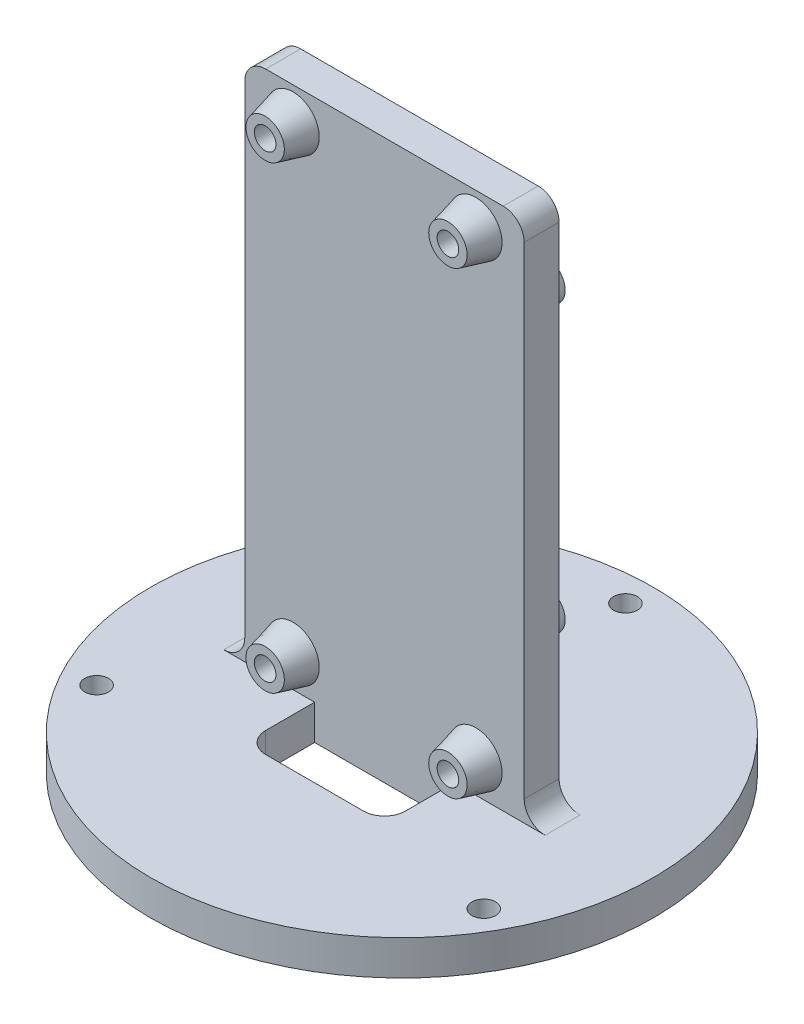
SolidWorks part; units mm, degrees
ref_plane "Front Plane" through (0, 0, 0) normal (0, 0, 1) x (1, 0, 0)
ref_plane "Top Plane" through (0, 0, 0) normal (0, 1, 0) x (1, 0, 0)
ref_plane "Right Plane" through (0, 0, 0) normal (1, 0, 0) x (0, 0, -1)
sketch "Sketch1" plane through (0, 0, 0) normal (0, 1, 0) x (1, 0, 0)
  circle A0 centre (0, 0) radius 36
  circle A1 centre (0, 32) radius 1.7
  circle A2 centre (0, 0) radius 32 construction
  circle A3 centre (27.7128, -16) radius 1.7
  circle A4 centre (-27.7128, -16) radius 1.7
  point P13 (0, 0)
  dimension "D1" = 64
  dimension "D2" = 72
  dimension "D3" = 3.4
  dimension "D4" = 3
extrude "Boss-Extrude1" add sketch "Sketch1" along normal blind 5
sketch "Sketch2" plane through (0, 0, 0) normal (0, 0, 1) x (1, 0, 0)
  line L0 (36, 5) -> (-36, 5) construction
  line L1 (-20, 5) -> (20, 5)
  line L2 (-20, 5) -> (-20, 80)
  line L3 (-20, 80) -> (20, 80)
  line L4 (20, 5) -> (20, 80)
  line L5 (0, 0) -> (0, 80) construction
  dimension "D1" = 40
  dimension "D2" = 75
extrude "Boss-Extrude2" add sketch "Sketch2" along normal mid plane 5
sketch "Sketch3" plane through (0, 0, 2.5) normal (0, 0, 1) x (1, 0, 0)
  line L0 (0, 80) -> (0, 0) construction
  line L1 (20, 80) -> (-20, 80) construction
  line L2 (-20, 42.5) -> (20, 42.5) construction
  line L3 (-13.085, 9.625) -> (13.085, 9.625) construction
  line L4 (-13.085, 9.625) -> (-13.085, 75.375) construction
  line L5 (-13.085, 75.375) -> (13.085, 75.375) construction
  line L6 (13.085, 9.625) -> (13.085, 75.375) construction
  line L7 (-13.085, 9.625) -> (13.085, 75.375) construction
  line L8 (-13.085, 75.375) -> (13.085, 9.625) construction
  line L9 (-20, 80) -> (-20, 5) construction
  line L10 (20, 5) -> (20, 80) construction
  circle A0 centre (-13.085, 75.375) radius 1.55
  circle A1 centre (13.085, 75.375) radius 1.55
  circle A2 centre (13.085, 9.625) radius 1.55
  circle A3 centre (-13.085, 9.625) radius 1.55
  circle A4 centre (-13.085, 75.375) radius 2.75
  circle A5 centre (13.085, 75.375) radius 2.75
  circle A6 centre (13.085, 9.625) radius 2.75
  circle A7 centre (-13.085, 9.625) radius 2.75
  point P5 (0, 42.5)
  dimension "D1" = 3.1
  dimension "D2" = 1.2
  dimension "D3" = 26.17
  dimension "D4" = 65.75
extrude "Boss-Extrude3" add sketch "Sketch3" along normal blind 4
sketch "Sketch4" plane through (0, 0, -2.5) normal (0, 0, -1) x (-1, 0, 0)
  line L0 (0, 80) -> (0, 0) construction
  line L1 (-20, 80) -> (20, 80) construction
  line L3 (-14.125, 65) -> (14.125, 65) construction
  line L4 (-14.125, 65) -> (-14.125, 24.15) construction
  line L5 (-14.125, 24.15) -> (14.125, 24.15) construction
  line L6 (14.125, 65) -> (14.125, 24.15) construction
  line L7 (-14.125, 65) -> (14.125, 24.15) construction
  line L8 (-14.125, 24.15) -> (14.125, 65) construction
  circle A0 centre (-14.125, 65) radius 2.75
  circle A1 centre (14.125, 65) radius 2.75
  circle A2 centre (14.125, 24.15) radius 2.75
  circle A3 centre (-14.125, 24.15) radius 2.75
  circle A4 centre (-14.125, 65) radius 1.55
  circle A5 centre (14.125, 65) radius 1.55
  circle A6 centre (14.125, 24.15) radius 1.55
  circle A7 centre (-14.125, 24.15) radius 1.55
  point P5 (0, 44.575)
  dimension "D4" = 3.1
  dimension "D5" = 1.2
  dimension "D1" = 28.25
  dimension "D2" = 40.85
  dimension "D3" = 15
extrude "Boss-Extrude4" add sketch "Sketch4" along normal blind 4
chamfer "Chamfer1" distance 1 distance2 4 8 edges at (11.375, 65, -2.5) (-16.875, 65, -2.5) (11.375, 24.15, -2.5) (-16.875, 24.15, -2.5) (10.335, 9.625, 2.5) (-15.835, 9.625, 2.5) (10.335, 75.375, 2.5) (-15.835, 75.375, 2.5) first distance on face at (11.375, 24.15, -2.5) first distance on face at (-15.835, 9.625, 2.5)
sketch "Sketch6" plane through (0, 5, 0) normal (0, 1, 0) x (1, 0, 0)
  line L0 (-20, 2.5) -> (20, 2.5) construction
  line L1 (-10, 2.5) -> (10, 2.5)
  line L2 (-10, 2.5) -> (-10, 12.5)
  line L3 (-10, 12.5) -> (10, 12.5)
  line L4 (10, 2.5) -> (10, 12.5)
  line L5 (-20, -2.5) -> (20, -2.5) construction
  line L6 (-10, -2.5) -> (10, -2.5)
  line L7 (-10, -2.5) -> (-10, -12.5)
  line L8 (-10, -12.5) -> (10, -12.5)
  line L9 (10, -2.5) -> (10, -12.5)
  line L10 (0, 0) -> (0, 12.5) construction
  dimension "D1" = 20
  dimension "D2" = 10
extrude "Cut-Extrude1" cut sketch "Sketch6" against normal through all
fillet "Fillet1" radius 3 8 edges at (-20, 5, 0) (-20, 80, 0) (20, 80, 0) (20, 5, 0) (-10, 2.5, 12.5) (10, 2.5, 12.5) (10, 2.5, -12.5) (-10, 2.5, -12.5)
